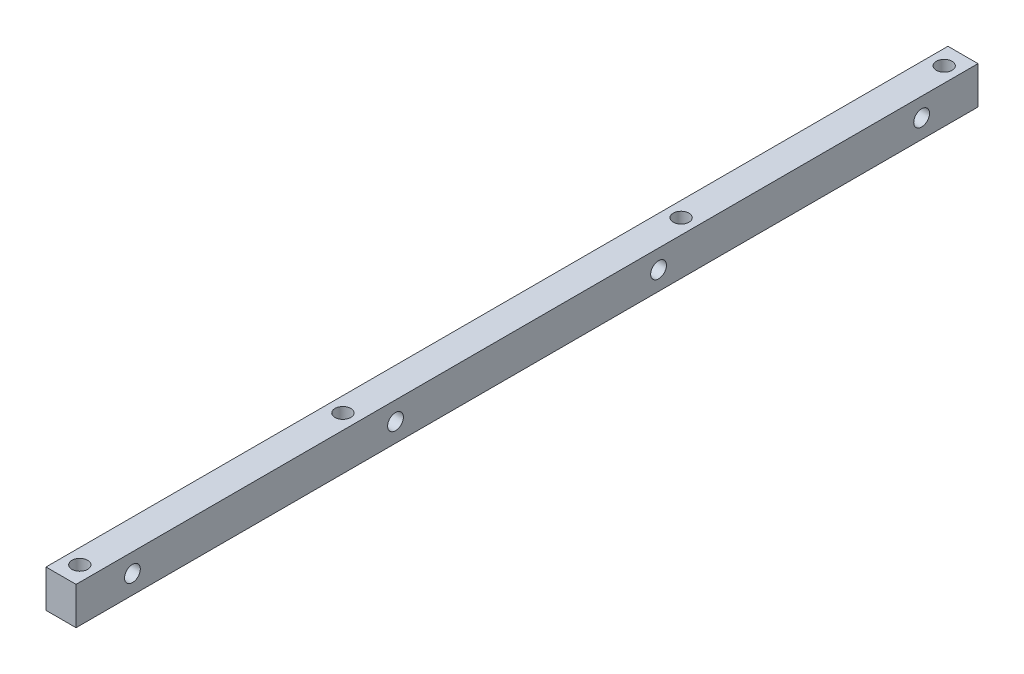
SolidWorks part; units mm, degrees
material "1060 Legierung"
ref_plane "Ebene vorne" through (0, 0, 0) normal (0, 0, 1) x (1, 0, 0)
ref_plane "Ebene oben" through (0, 0, 0) normal (0, 1, 0) x (1, 0, 0)
ref_plane "Ebene rechts" through (0, 0, 0) normal (1, 0, 0) x (0, 0, -1)
sketch "Skizze1" plane through (0, 0, 0) normal (0, 0, 1) x (1, 0, 0)
  line L0 (0, 23.6064) -> (0, -30.9834) construction
  line L1 (-21.3308, 0) -> (37.1933, 0) construction
  line L2 (-4, 5) -> (4, 5)
  line L3 (4, 5) -> (4, -5)
  line L4 (4, -5) -> (-4, -5)
  line L5 (-4, -5) -> (-4, 5)
  dimension "D1" = 8
  dimension "D2" = 10
extrude "Aufsatz-Linear austragen1" add sketch "Skizze1" along normal blind 120 and the other way blind 120
hole_wizard "M5 Gewindebohrung1" positions "Skizze3" profile "Skizze2" tap size "M5" standard "Din" end condition through all
sketch "Skizze3" plane through (0, 5, 0) normal (0, 1, 0) x (1, 0, 0)
  line L0 (-11.9752, 0) -> (18.2305, 0) construction
  point P0 (0, -115)
  point P2 (0, -45)
  dimension "D1" = 45
  dimension "D2" = 115
sketch "Skizze2" plane through (0, 5, 115) normal (1, 0, 0) x (0, 0, 1)
  line L0 (0, 0) -> (0, 10)
  line L1 (0, 10) -> (2.1, 10)
  line L2 (2.1, 10) -> (2.1, 0)
  line L5 (2.1, 0) -> (0, 0)
  line L11 (0, -6.35) -> (0, 107.95) construction
  dimension "Bohrerdurchmesser" = 4.2
  dimension "Bohrungstiefe" = 10
cosmetic thread "Bohrungsgewinde1" parameters "D2"=5
cosmetic thread "Bohrungsgewinde2" parameters "D2"=5
hole_wizard "Ø4.2 (4.2) Durchmesser Bohrung1" positions "Skizze5" profile "Skizze4" hole size "Ø4.2" standard "Din"
sketch "Skizze5" plane through (-4, 0, 0) normal (-1, 0, 0) x (0, 0, 1)
  line L0 (0, -13.7441) -> (0, 14.4835) construction
  point P0 (105, 0)
  point P2 (35, 0)
  dimension "D1" = 35
  dimension "D2" = 105
sketch "Skizze4" plane through (-4, 0, 105) normal (0, 1, 0) x (0, 0, 1)
  line L0 (0, 0) -> (0, 11.2618)
  line L1 (0, 11.2618) -> (2.1, 10)
  line L2 (2.1, 10) -> (2.1, 0)
  line L5 (2.1, 0) -> (0, 0)
  line L10 (0, 11.2618) -> (-2.1, 10) construction
  line L11 (0, -6.35) -> (0, 107.95) construction
  dimension "Bohrerdurchmesser" = 4.2
  dimension "Bohrungstiefe" = 10
  dimension "Spitzenwinkel" = 118
mirror "Spiegeln1" about plane through (0, 0, 0) normal (0, 0, 1) of "Ø4.2 (4.2) Durchmesser Bohrung1", "M5 Gewindebohrung1"
